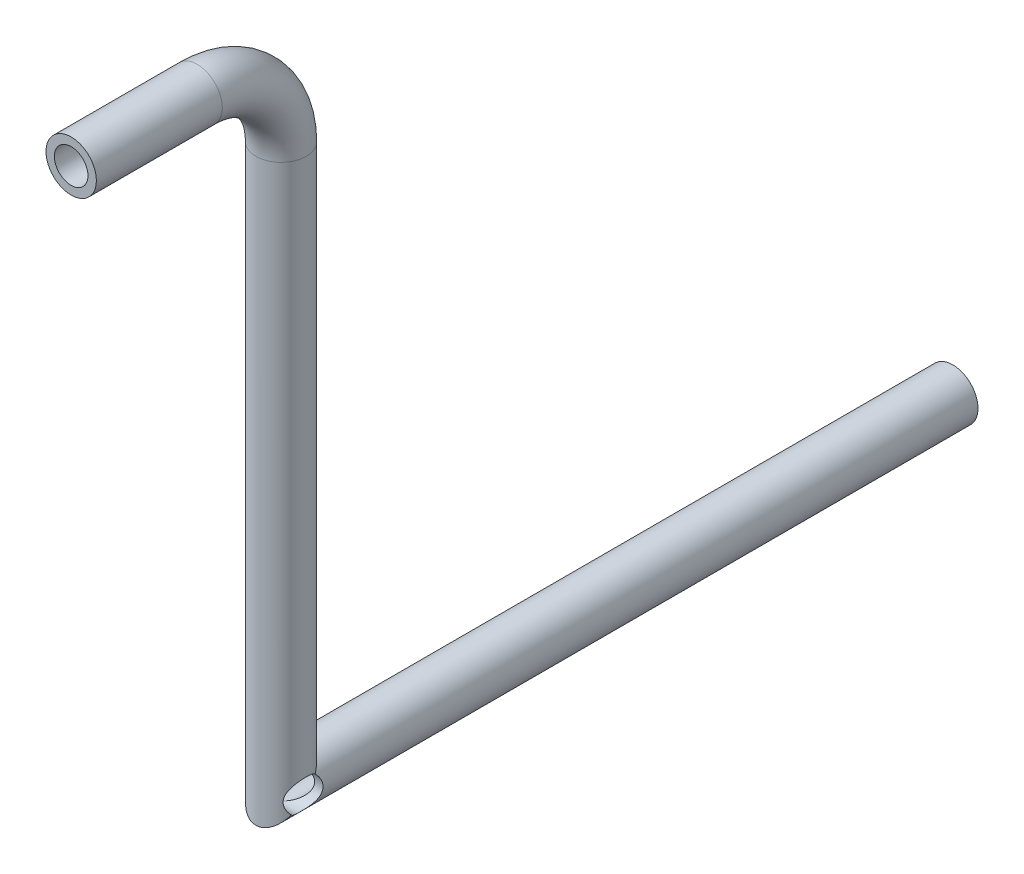
SolidWorks part; units mm, degrees
ref_plane "Front Plane" through (0, 0, 0) normal (0, 0, 1) x (1, 0, 0)
ref_plane "Top Plane" through (0, 0, 0) normal (0, 1, 0) x (1, 0, 0)
ref_plane "Right Plane" through (0, 0, 0) normal (1, 0, 0) x (0, 0, -1)
sketch "Sketch1" plane through (0, 0, 0) normal (1, 0, 0) x (0, 0, -1)
  line L0 (-41.8719, 668.2512) -> (108.1281, 668.2512)
  line L1 (208.1281, 568.2512) -> (208.1281, -91.7488)
  line L2 (208.1281, -91.7488) -> (1008.1281, -91.7488)
  arc A0 (108.1281, 668.2512) -> (208.1281, 568.2512) centre (108.1281, 568.2512) cw
  point P6 (208.1281, 668.2512)
  dimension "D4" = 100
  dimension "D1" = 250
  dimension "D2" = 760
  dimension "D3" = 800
sweep "Sweep-Thin1" add path "Sketch1" circular profile diameter 60 parameters "D1"=10, "D3"=60
sketch "Sketch3" plane through (0, 0, 0) normal (1, 0, 0) x (0, 0, -1)
  line L0 (178.1281, -121.7488) -> (238.1281, -61.7488) construction
  circle A0 centre (208.1281, -91.7488) radius 20
extrude "Cut-Extrude1" cut sketch "Sketch3" against normal through all both and the other way through all
ref_plane "Plane1" through (0, 0, -330) normal (0, 0, 1) x (1, 0, 0)
sketch "Sketch5" plane through (0, 0, -330) normal (0, 0, 1) x (1, 0, 0)
  circle A0 centre (0, 383.2512) radius 20
  arc A1 (-26.4575, -105.8909) -> (26.4575, -105.8909) centre (0, -91.7488) ccw construction
  dimension "D2" = 40
  dimension "D1" = 475
extrude "Cut-Extrude3" cut sketch "Sketch5" along normal blind 111
